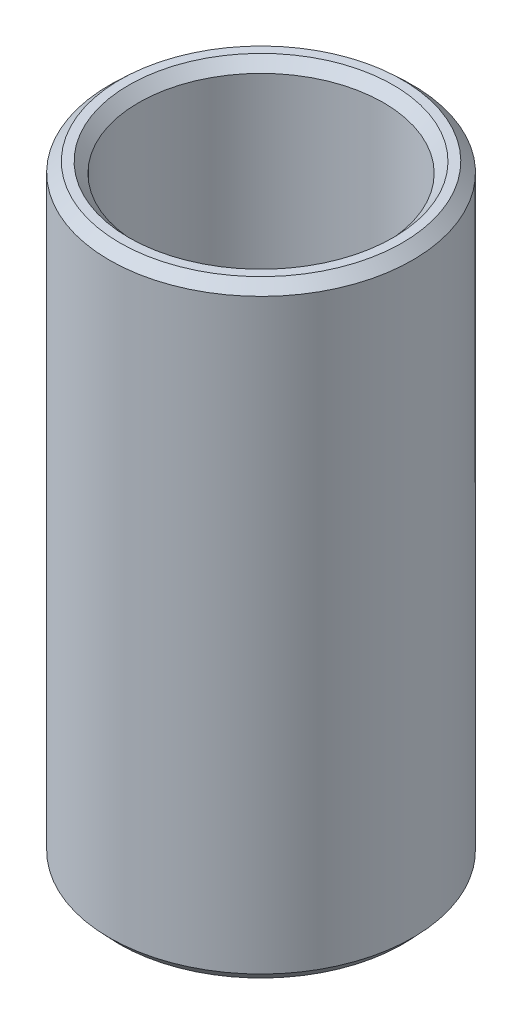
SolidWorks part; units mm, degrees
ref_plane "Front Plane" through (0, 0, 0) normal (0, 0, 1) x (1, 0, 0)
ref_plane "Top Plane" through (0, 0, 0) normal (0, 1, 0) x (1, 0, 0)
ref_plane "Right Plane" through (0, 0, 0) normal (1, 0, 0) x (0, 0, -1)
sketch "Sketch1" plane through (0, 0, 0) normal (0, 1, 0) x (1, 0, 0)
  circle A0 centre (0, 0) radius 57.5
  dimension "SLEEVE_OD" = 115
extrude "Boss-Extrude1" add sketch "Sketch1" along normal blind 230.1979
sketch "Sketch2" plane through (0, 0, 0) normal (0, 1, 0) x (1, 0, 0)
  circle A0 centre (0, 0) radius 46.4294
  dimension "BORE_D" = 92.8588
extrude "Cut-Extrude1" cut sketch "Sketch2" along normal through all
chamfer "Chamfer1" distance 3.7076 angle 46.707 4 edges at (0, 230.1979, 46.4294) (0, 0, 46.4294) (0, 0, 57.5) (0, 230.1979, 57.5) first distance on face at (0, 230.1979, 46.4294) first distance on face at (0, 0, 46.4294) first distance on face at (0, 230.1979, 57.5)
